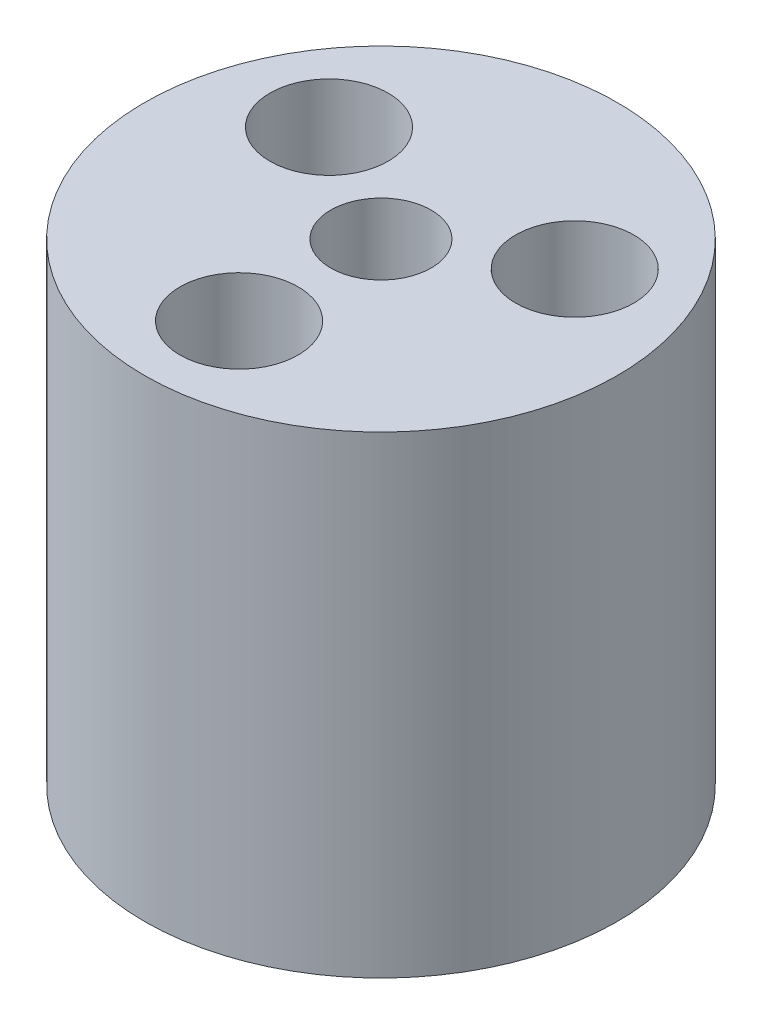
SolidWorks part; units mm, degrees
ref_plane "Front Plane" through (0, 0, 0) normal (0, 0, 1) x (1, 0, 0)
ref_plane "Top Plane" through (0, 0, 0) normal (0, 1, 0) x (1, 0, 0)
ref_plane "Right Plane" through (0, 0, 0) normal (1, 0, 0) x (0, 0, -1)
sketch "Sketch1" plane through (0, 0, 0) normal (0, 1, 0) x (1, 0, 0)
  line L0 (-14.8133, 0) -> (725.8506, 0) construction
  line L1 (0, -14.8133) -> (0, 725.8506) construction
  circle A0 centre (0, 0) radius 10
  dimension "D1" = 20
extrude "Boss-Extrude1" add sketch "Sketch1" along normal blind 20
sketch "Sketch2" plane through (0, 20, 0) normal (0, 1, 0) x (1, 0, 0)
  line L0 (-1000, 0) -> (49000, 0) construction
  line L1 (0, -1000) -> (0, 49000) construction
  line L2 (-868.8835, -501.6501) -> (42432.3867, 24498.3499) construction
  line L3 (868.9864, -501.7095) -> (-42432.2838, 24498.2905) construction
  circle A0 centre (0, -6) radius 2.5
  circle A1 centre (0, 0) radius 10
  circle A2 centre (0, 0) radius 10
  circle A3 centre (-5.1962, 3) radius 2.5
  circle A4 centre (5.1962, 3) radius 2.5
  circle A5 centre (0, 0) radius 2.125
  dimension "D3" = 5
  dimension "D8" = 4.25
  dimension "D2" = 6
  dimension "D4" = 120
  dimension "D5" = 120
  dimension "D6" = 6
  dimension "D7" = 6
  dimension "D1" = 0
extrude "Cut-Extrude1" cut sketch "Sketch2" against normal blind 10 contours A3 | A0 | A4 region at (0, 20, 6) region at (-5.1962, 20, -3) region at (5.1962, 20, -3)
extrude "Cut-Extrude2" cut sketch "Sketch2<3>" against normal through all contours A5 region at (0, 20, 0)
sketch "Sketch2<3>" plane through (0, 20, 0) normal (0, 1, 0) x (1, 0, 0) same geometry as "Sketch2"
